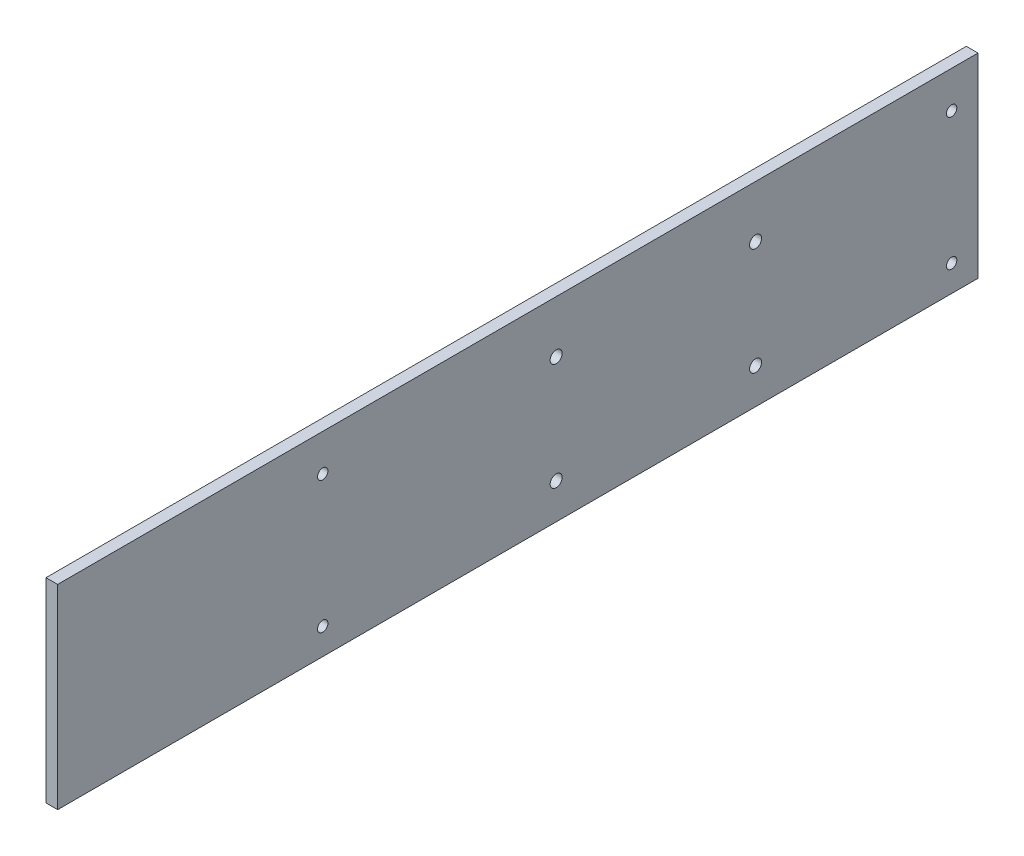
SolidWorks part; units mm, degrees
material "6061-T6 (SS)"
ref_plane "Front Plane" through (0, 0, 0) normal (0, 0, 1) x (1, 0, 0)
ref_plane "Top Plane" through (0, 0, 0) normal (0, 1, 0) x (1, 0, 0)
ref_plane "Right Plane" through (0, 0, 0) normal (1, 0, 0) x (0, 0, -1)
sketch "Sketch1" plane through (0, 0, 0) normal (1, 0, 0) x (0, 0, -1)
  line L1 (-190.5, 38.1) -> (190.5, 38.1)
  line L2 (-190.5, 38.1) -> (-190.5, -38.1)
  line L3 (-190.5, -38.1) -> (190.5, -38.1)
  line L4 (190.5, 38.1) -> (190.5, -38.1)
  line L5 (-190.5, 38.1) -> (190.5, -38.1) construction
  line L6 (-190.5, -38.1) -> (190.5, 38.1) construction
  point P0 (0, 0)
  dimension "D1" = 76.2
  dimension "D2" = 381
extrude "Boss-Extrude1" add sketch "Sketch1" along normal blind 4.826
sketch "Sketch2" plane through (4.826, 0, 0) normal (1, 0, 0) x (0, 0, -1)
  line L0 (190.5, -38.1) -> (190.5, 38.1) construction
  line L1 (-80.772, 22.86) -> (179.578, 22.86) construction
  line L2 (-80.772, 22.86) -> (-80.772, -31.75) construction
  line L3 (-80.772, -31.75) -> (179.578, -31.75) construction
  line L4 (179.578, 22.86) -> (179.578, -31.75) construction
  line L5 (-80.772, 22.86) -> (179.578, -31.75) construction
  line L6 (-80.772, -31.75) -> (179.578, 22.86) construction
  line L7 (-190.5, 38.1) -> (-190.5, -38.1) construction
  line L8 (15.875, -27.94) -> (98.425, -27.94) construction
  line L9 (-190.5, -38.1) -> (190.5, -38.1) construction
  line L11 (15.875, -27.94) -> (98.425, -27.94) construction
  line L12 (15.875, -27.94) -> (15.875, 16.51) construction
  line L13 (15.875, 16.51) -> (98.425, 16.51) construction
  line L14 (98.425, -27.94) -> (98.425, 16.51) construction
  point P0 (49.403, -4.445)
  point P7 (0, 0)
  point P17 (-185.293, 4.0792)
  point P18 (-173.736, -2.413)
  dimension "D1" = 10.922
  dimension "D2" = 260.35
  dimension "D3" = 54.61
  dimension "D4" = 10.16
  dimension "D5" = 82.55
  dimension "D6" = 92.075
  dimension "D7" = 44.45
  dimension "D8" = 5.207
  dimension "D9" = 42.1792
  dimension "D10" = 6.35
  dimension "D11" = 35.687
  dimension "D12" = 16.764
hole_wizard "#10 Clearance Hole1" positions "Sketch3" profile "Sketch4" hole size "#10" standard "ANSI Inch" end condition through all
sketch "Sketch3" plane through (4.826, 0, 0) normal (1, 0, 0) x (0, 0, -1)
  point P12 (98.425, -27.94)
  point P15 (15.875, -27.94)
  point P18 (15.875, 16.51)
  point P21 (98.425, 16.51)
sketch "Sketch4" plane through (4.826, -27.94, -98.425) normal (0, 1, 0) x (0, 0, -1)
  line L0 (0, 0) -> (0, 4.826)
  line L1 (0, 4.826) -> (2.4892, 4.826)
  line L2 (2.4892, 4.826) -> (2.4892, 0)
  line L5 (2.4892, 0) -> (0, 0)
  line L11 (0, -6.35) -> (0, 107.95) construction
  dimension "Thru Hole Dia." = 4.9784
  dimension "Thru Hole Depth" = 4.826
hole_wizard "#8 Clearance Hole1" positions "Sketch17" profile "Sketch18" hole size "#8" standard "ANSI Inch"
sketch "Sketch17" plane through (4.826, 0, 0) normal (1, 0, 0) x (0, 0, -1)
  point P3 (-80.772, 22.86)
  point P6 (-80.772, -31.75)
  point P9 (179.578, -31.75)
  point P12 (179.578, 22.86)
sketch "Sketch18" plane through (4.826, 22.86, 80.772) normal (0, 1, 0) x (0, 0, -1)
  line L0 (0, 0) -> (0, 13.9934)
  line L1 (0, 13.9934) -> (2.1526, 12.7)
  line L2 (2.1526, 12.7) -> (2.1526, 0)
  line L5 (2.1526, 0) -> (0, 0)
  line L10 (0, 13.9934) -> (-2.1527, 12.7) construction
  line L11 (0, -6.35) -> (0, 107.95) construction
  dimension "Hole Dia." = 4.3053
  dimension "Hole Depth" = 12.7
  dimension "Drill Angle" = 118
sketch "Sketch31" plane through (0, -38.1, 0) normal (0, -1, 0) x (1, 0, 0)
  line L1 (4.826, 190.5) -> (0, 190.5)
  line L2 (4.826, 190.5) -> (4.826, -190.5)
  line L3 (4.826, -190.5) -> (0, -190.5)
  line L4 (0, 190.5) -> (0, -190.5)
extrude "Boss-Extrude10" add sketch "Sketch31" along normal blind 4.572
sketch "Sketch5" plane through (4.826, 0, 0) normal (1, 0, 0) x (0, 0, -1)
  circle A0 centre (-80.772, 22.86) radius 6.35
  circle A1 centre (-80.772, -31.75) radius 6.35
  circle A2 centre (179.578, 22.86) radius 6.35
  circle A3 centre (179.578, -31.75) radius 6.35
  circle A4 centre (98.425, -27.94) radius 6.35
  circle A5 centre (15.875, -27.94) radius 6.35
  circle A6 centre (15.875, 16.51) radius 6.35
  circle A7 centre (98.425, 16.51) radius 6.35
  circle A8 centre (-185.293, 4.0792) radius 4.7625
  circle A9 centre (-173.736, -2.413) radius 3.2639
  circle A10 centre (-173.736, -2.413) radius 6.4158
  circle A11 centre (-185.293, 4.0792) radius 2.0098
  dimension "D4" = 12.7
  dimension "D2" = 9.525
  dimension "D3" = 6.5278
  dimension "D5" = 12.8316
  dimension "D6" = 4.0196
